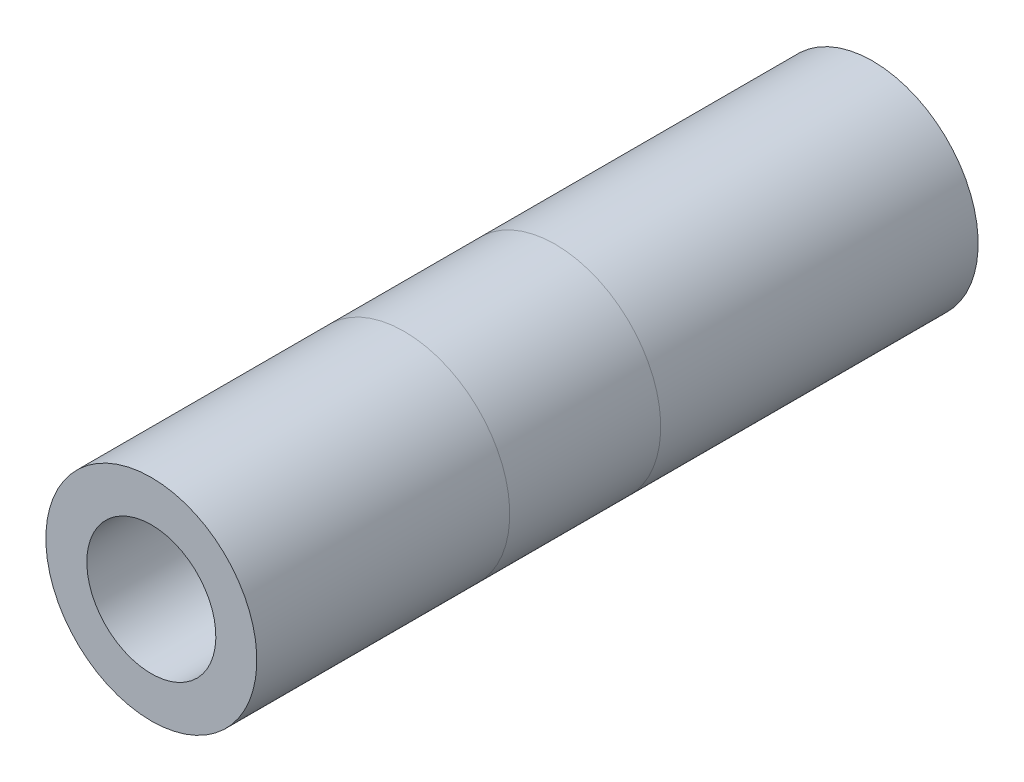
SolidWorks part; units mm, degrees
material "Silicon Rubber"
ref_plane "X-Y Datum" through (0, 0, 0) normal (0, 0, 1) x (1, 0, 0)
ref_plane "X-Z Datum" through (0, 0, 0) normal (0, 1, 0) x (1, 0, 0)
ref_plane "Y-Z Datum" through (0, 0, 0) normal (1, 0, 0) x (0, 0, -1)
sketch3d "3DSketch1"
  line L0 (-46.03, 0, -24.6) -> (-46.03, 0, 0)
  line L1 (-46.03, 0, 0) -> (-46.03, 0, 11.7)
  line L2 (-46.03, 0, 31.3016) -> (-46.03, 0, 11.7)
sweep "Sweep1" add path "3DSketch1" circular profile diameter 16.35 parameters "D3"=16.35
sweep "Cut-Sweep1" cut path "3DSketch1<2>" circular profile diameter 10 parameters "D3"=10
sketch3d "3DSketch1<2>" same geometry as "3DSketch1"
sketch3d "3DSketch2"
  circle A1 centre (-46.03, 0, 0) radius 5 construction
  circle A2 centre (-46.03, 0, 0) radius 5 construction
  circle A3 centre (-46.03, 0, 11.7) radius 5 construction
  circle A5 centre (-46.03, 0, 11.7) radius 5 construction
  point P2 (-46.03, 0, -5)
  point P4 (-46.03, 0, -5)
  point P5 (0, 0, 0)
  point P9 (-46.03, 0, 6.7)
  point P12 (-46.03, 0, 6.7)
